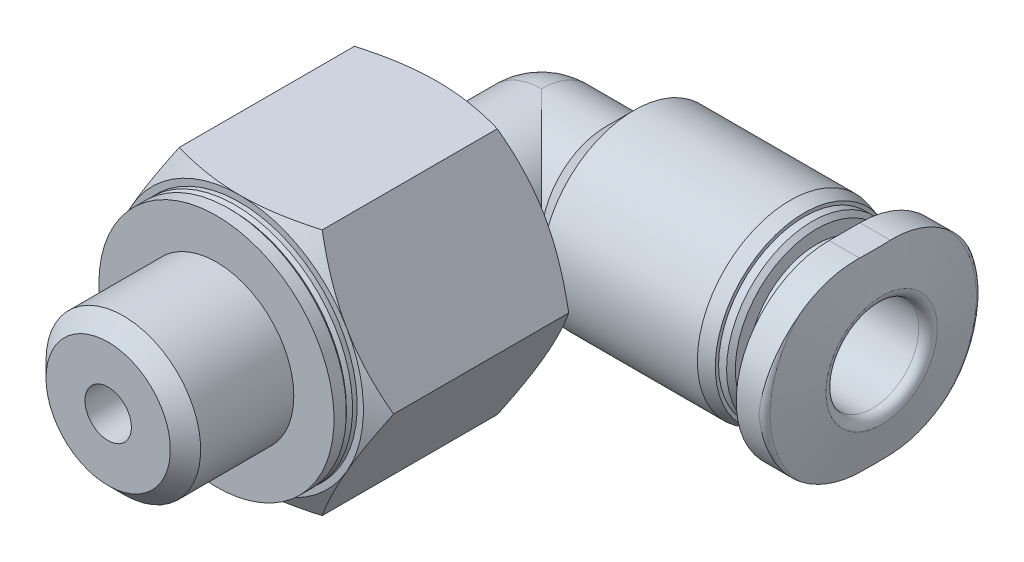
SolidWorks part; units mm, degrees
ref_plane "Ebene vorne" through (0, 0, 0) normal (0, 0, 1) x (1, 0, 0)
ref_plane "Ebene oben" through (0, 0, 0) normal (0, 1, 0) x (1, 0, 0)
ref_plane "Ebene rechts" through (0, 0, 0) normal (1, 0, 0) x (0, 0, -1)
sketch "Skizze1" plane through (0, 0, 0) normal (0, 0, 1) x (1, 0, 0)
  line L0 (0, 2.1) -> (2.1, 2.1)
  line L1 (2.1, 2.1) -> (3, 3)
  line L2 (3, 3) -> (8.0429, 3)
  line L3 (8.0429, 3) -> (8.5, 2.8775)
  line L4 (8.5, 2.8775) -> (8.5, 2.7703)
  line L5 (8.5, 2.7703) -> (8.7586, 2.7703)
  line L6 (8.7586, 2.7703) -> (8.9, 2.6289)
  line L7 (8.9, 2.6289) -> (8.9, 2.2)
  line L8 (8.9, 2.2) -> (9.43, 2.2)
  line L9 (9.8, 2.57) -> (9.8, 3.5)
  line L10 (9.8, 3.5) -> (10.5324, 3.5)
  line L11 (10.7294, 3.3347) -> (11, 1.8)
  line L12 (11, 1.8) -> (11, 0)
  line L13 (11, 0) -> (-2.1, 0)
  line L14 (11, 0) -> (-2.1, 0) construction
  arc A0 (-2.1, 0) -> (0, 2.1) centre (0, 0) cw
  arc A1 (9.43, 2.2) -> (9.8, 2.57) centre (9.43, 2.57) ccw
  arc A2 (10.5324, 3.5) -> (10.7294, 3.3347) centre (10.5324, 3.3) cw
revolve "Rotation1" add sketch "Skizze1" angle 360 about L14
sketch "Skizze2" plane through (0, 0, 0) normal (1, 0, 0) x (0, 0, -1)
  line L0 (-10.5, 0) -> (-10.5, 3.8)
  line L1 (-10.5, 3.8) -> (-10.1, 3.8)
  line L2 (-10.1, 3.8) -> (-10, 3.7)
  line L3 (-10, 3.7) -> (-9.9, 3.8)
  line L4 (-9.9, 3.8) -> (-9.75, 3.8)
  line L5 (-9.75, 3.8) -> (-9.75, 4)
  line L6 (-9.75, 4) -> (-9.3805, 4.64)
  line L7 (-9.3805, 4.64) -> (-3.7445, 4.64)
  line L8 (-3.7445, 4.64) -> (-3.375, 4)
  line L9 (-3.375, 4) -> (-3.375, 2.25)
  line L10 (-3.375, 2.25) -> (-2.8, 2.25)
  line L11 (-2.8, 2.25) -> (-2.65, 2.1)
  line L12 (-2.65, 2.1) -> (0, 2.1)
  line L13 (0, 2.1) -> (0, 0)
  line L14 (0, 0) -> (-10.5, 0)
  line L15 (0, 0) -> (-10.5, 0) construction
revolve "Rotation2" add sketch "Skizze2" angle 360 about L15
sketch "Skizze3" plane through (0, 0, 0) normal (1, 0, 0) x (0, 0, -1)
  line L0 (-14, 0) -> (-14, 2.0095)
  line L1 (-14, 2.0095) -> (-13.5095, 2.5)
  line L2 (-13.5095, 2.5) -> (-10.5, 2.5)
  line L3 (-10.5, 2.5) -> (-10.5, 0)
  line L4 (-10.5, 0) -> (-14, 0)
  line L5 (-10.5, 0) -> (-14, 0) construction
revolve "Rotation3" add sketch "Skizze3" angle 360 about L5
cosmetic thread "Gewindedarstellung1" parameters "D1"=3.5, "D2"=4.019
ref_plane "Ebene1" through (11, 0, 0) normal (1, 0, 0) x (0, 0, -1)
sketch "Skizze4" plane through (11, 0, 0) normal (1, 0, 0) x (0, 0, -1)
  line L0 (-4.2, 2.4249) -> (-4.2, -2.4249)
  line L1 (-4.2, -2.4249) -> (0, -4.8497)
  line L2 (0, -4.8497) -> (4.2, -2.4249)
  line L3 (4.2, -2.4249) -> (4.2, 2.4249)
  line L4 (4.2, 2.4249) -> (0, 4.8497)
  line L5 (0, 4.8497) -> (-4.2, 2.4249)
  line L6 (-0.5, -3) -> (0.5, -3)
  line L7 (0.5, 3) -> (-0.5, 3)
  arc A0 (-3.5, 0) -> (-0.5, -3) centre (-0.5, 0) ccw
  arc A1 (0.5, -3) -> (3.5, 0) centre (0.5, 0) ccw
  arc A2 (3.5, 0) -> (0.5, 3) centre (0.5, 0) ccw
  arc A3 (-0.5, 3) -> (-3.5, 0) centre (-0.5, 0) ccw
extrude "Linear austragen1" cut sketch "Skizze4" against normal blind 1.2
sketch "Skizze5" plane through (0, 0, 0) normal (0, 1, 0) x (1, 0, 0)
  line L0 (0, 0.75) -> (1.5, 0.75)
  line L1 (1.5, 0.75) -> (1.5, 1.5)
  line L2 (1.5, 1.5) -> (10.7, 1.5)
  line L3 (11, 1.8) -> (11, 0)
  line L4 (11, 0) -> (-0.75, 0)
  line L5 (11, 0) -> (-0.75, 0) construction
  arc A0 (-0.75, 0) -> (0, 0.75) centre (0, 0) cw
  arc A1 (10.7, 1.5) -> (11, 1.8) centre (10.7, 1.8) ccw
sketch "Skizze6" plane through (0, 0, 0) normal (1, 0, 0) x (0, 0, -1)
  line L0 (-14, 0) -> (-14, 0.75)
  line L1 (-14, 0.75) -> (0, 0.75)
  line L2 (0, 0.75) -> (0, 0)
  line L3 (0, 0) -> (-14, 0)
  line L4 (0, 0) -> (-14, 0) construction
revolve "Schnitt-Rotation1" cut sketch "Skizze6" angle 360 about L4
revolve "Schnitt-Rotation2" cut sketch "Skizze5" angle 360 about L5
ref_plane "Ebene2" through (0, 0, 10.5) normal (0, 0, 1) x (1, 0, 0)
sketch "Skizze7" plane through (0, 0, 10.5) normal (0, 0, 1) x (1, 0, 0)
  line L0 (-8, 8) -> (-8, -8)
  line L1 (-8, -8) -> (8, -8)
  line L2 (8, -8) -> (8, 8)
  line L3 (8, 8) -> (-8, 8)
  line L4 (-4.6188, 0) -> (-2.3094, -4)
  line L5 (-2.3094, -4) -> (2.3094, -4)
  line L6 (2.3094, -4) -> (4.6188, 0)
  line L7 (4.6188, 0) -> (2.3094, 4)
  line L8 (2.3094, 4) -> (-2.3094, 4)
  line L9 (-2.3094, 4) -> (-4.6188, 0)
extrude "Linear austragen2" cut sketch "Skizze7" against normal blind 7.1667
ref_plane "Ebene3" through (0, 0, 10.5) normal (0, 0, 1) x (1, 0, 0)
ref_plane "Ebene4" through (1.5, 0, 0) normal (1, 0, 0) x (0, 0, -1)
ref_plane "ANBAU XY" through (0, 0, 10.5) normal (0, 0, 1) x (1, 0, 0)
ref_plane "ANBAU XZ" through (0, 0, 0) normal (0, -1, 0) x (1, 0, 0)
ref_plane "ANBAU YZ" through (0, 0, 0) normal (1, 0, 0) x (0, 0, -1)
ref_axis "ANBAU X" through (-80.9, 0, 10.5) along (1, 0, 0)
ref_axis "ANBAU Y" through (0, -50, 10.5) along (0, 1, 0)
ref_axis "ANBAU Z" through (0, 0, 80.9) along (0, 0, -1)
sketch3d "ANBAU"
  point P0 (0, 0, 10.5)
ref_plane "CPV XY" through (0, 0, 10.5) normal (0, 0, -1) x (-1, 0, 0)
ref_plane "CPV XZ" through (0, 0, 0) normal (0, 1, 0) x (-1, 0, 0)
ref_plane "CPV YZ" through (0, 0, 0) normal (1, 0, 0) x (0, 0, -1)
ref_axis "CPV X" through (-80.9, 0, 10.5) along (1, 0, 0)
ref_axis "CPV Y" through (0, 50, 10.5) along (0, -1, 0)
ref_axis "CPV Z" through (0, 0, -80.9) along (0, 0, 1)
sketch3d "CPV"
  point P0 (0, 0, 10.5)
ref_plane "FDT_SCHLAUCH XY" through (1.5, 0, 0) normal (1, 0, 0) x (0, 0, -1)
ref_plane "FDT_SCHLAUCH XZ" through (0, 0, 0) normal (0, -1, 0) x (1, 0, 0)
ref_plane "FDT_SCHLAUCH YZ" through (0, 0, 0) normal (0, 0, -1) x (-1, 0, 0)
ref_axis "FDT_SCHLAUCH X" through (1.5, 0, 80.9) along (0, 0, -1)
ref_axis "FDT_SCHLAUCH Y" through (1.5, -50, 0) along (0, 1, 0)
ref_axis "FDT_SCHLAUCH Z" through (80.9, 0, 0) along (-1, 0, 0)
sketch3d "FDT_SCHLAUCH"
  point P0 (1.5, 0, 0)
